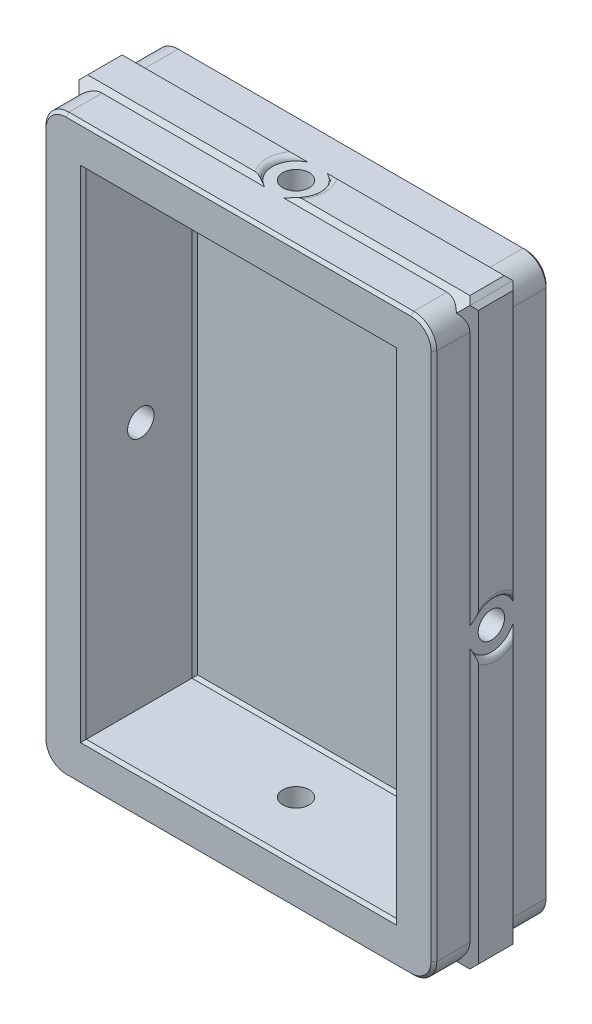
SolidWorks part; units mm, degrees
ref_plane "Front" through (0, 0, 0) normal (0, 0, 1) x (1, 0, 0)
ref_plane "Top" through (0, 0, 0) normal (0, 1, 0) x (1, 0, 0)
ref_plane "Right" through (0, 0, 0) normal (1, 0, 0) x (0, 0, -1)
sketch "Skizze1" plane through (0, 0, 0) normal (0, 0, 1) x (1, 0, 0)
  line L0 (61, 7) -> (7, 93) construction
  line L1 (0, 0) -> (68, 0)
  line L2 (0, 0) -> (0, 100)
  line L3 (0, 100) -> (68, 100)
  line L4 (68, 0) -> (68, 100)
  line L5 (11.1328, 7) -> (56.8672, 7)
  line L6 (7, 13.5818) -> (7, 86.4182)
  line L7 (11.1328, 93) -> (56.8672, 93)
  line L8 (61, 13.5818) -> (61, 86.4182)
  line L9 (61, 93) -> (7, 7) construction
  line L10 (11.1328, 93) -> (34, 56.5818)
  line L11 (7, 86.4182) -> (29.8672, 50)
  line L12 (56.8672, 93) -> (34, 56.5818)
  line L13 (11.1328, 7) -> (34, 43.4182)
  line L14 (38.1328, 50) -> (61, 86.4182)
  line L15 (38.1328, 50) -> (61, 13.5818)
  line L16 (29.8672, 50) -> (7, 13.5818)
  line L17 (34, 43.4182) -> (56.8672, 7)
  line L18 (7, 86.4182) -> (7, 93)
  line L19 (7, 93) -> (11.1328, 93)
  line L20 (56.8672, 93) -> (61, 93)
  line L21 (61, 93) -> (61, 86.4182)
  line L22 (61, 13.5818) -> (61, 7)
  line L23 (61, 7) -> (56.8672, 7)
  line L24 (11.1328, 7) -> (7, 7)
  line L25 (7, 7) -> (7, 13.5818)
  dimension "D1" = 7
  dimension "D2" = 7
  dimension "D3" = 7
  dimension "D4" = 7
  dimension "D5" = 3.5
  dimension "D6" = 3.5
  dimension "D7" = 3.5
  dimension "D8" = 3.5
extrude "Aufsatz-Linear austragen1" add sketch "Skizze1" along normal blind 20 contours L1 L4 L3 L2 L24 L25 L6 L18 L19 L7 L20 L21 L8 L22 L23 L5 region at (1.2093, 50, 0)
sketch "Skizze2" plane through (0, 0, 0) normal (0, 0, 1) x (1, 0, 0)
  line L1 (0, 100) -> (68, 100)
  line L2 (0, 100) -> (0, 0)
  line L3 (0, 0) -> (68, 0)
  line L4 (68, 100) -> (68, 0)
extrude "Aufsatz-Linear austragen2" add sketch "Skizze2" along normal blind 0.6
sketch "Skizze3" plane through (0, 0, 0) normal (0, -1, 0) x (1, 0, 0)
  line L0 (0, 10) -> (-11.2685, 10) construction
  line L1 (0, 20) -> (0, 0) construction
  line L2 (34, 0) -> (34, 20) construction
  line L5 (0, 13.75) -> (-0.75, 13)
  line L6 (-0.75, 13) -> (-0.75, 7)
  line L7 (0, 13.75) -> (0, 6.25)
  line L8 (0, 6.25) -> (-0.75, 7)
  line L9 (68, 13.75) -> (68.75, 13)
  line L10 (68.75, 13) -> (68.75, 7)
  line L11 (68, 6.25) -> (68.75, 7)
  line L12 (68, 13.75) -> (68, 6.25)
  line L13 (0, 20) -> (68, 20) construction
  line L14 (0, 0) -> (68, 0) construction
  point P15 (-0.75, 10)
  dimension "D1" = 45
  dimension "D2" = 7.5
  dimension "D3" = 0.75
extrude "Aufsatz-Linear austragen3" add sketch "Skizze3" against normal up to surface (100 mm away) up to face at (34, 100, 10)
sketch "Skizze4" plane through (0, 0, 0) normal (-1, 0, 0) x (0, 0, 1)
  line L0 (10, 100) -> (10, 106.8008) construction
  line L1 (7, 100) -> (13, 100) construction
  line L2 (13.75, 100) -> (13, 100.75)
  line L3 (13, 100.75) -> (7, 100.75)
  line L4 (13.75, 100) -> (6.25, 100)
  line L5 (6.25, 100) -> (7, 100.75)
  line L6 (0, 50) -> (20, 50) construction
  line L8 (13.75, 0) -> (13, -0.75)
  line L9 (13, -0.75) -> (7, -0.75)
  line L10 (6.25, 0) -> (7, -0.75)
  line L11 (13.75, 0) -> (6.25, 0)
  line L12 (0, 0) -> (0, 100) construction
  point P10 (10, 100.75)
  dimension "D1" = 0.75
  dimension "D2" = 45
extrude "Aufsatz-Linear austragen4" add sketch "Skizze4" against normal up to surface (68 mm away) up to face at (68, 50, 3.125)
sketch "Skizze5" plane through (0, 93, 0) normal (0, -1, 0) x (1, 0, 0)
  line L0 (34, 0) -> (34, 20) construction
  line L3 (0, 20) -> (68, 20) construction
  line L4 (0, 0) -> (68, 0) construction
  circle A0 centre (34, 10) radius 2.3
  dimension "D1" = 4.6
extrude "Schnitt-Linear austragen1" cut sketch "Skizze5" against normal blind 20
ref_plane "Ebene1" through (0, 50, 0) normal (0, 1, 0) x (1, 0, 0)
ref_plane "Ebene2" through (34, 0, 0) normal (-1, 0, 0) x (0, 0, 1)
sketch "Skizze6" plane through (7, 0, 0) normal (1, 0, 0) x (0, 0, -1)
  line L0 (-20, 50) -> (0, 50) construction
  line L3 (-20, 0) -> (-20, 100) construction
  line L4 (0, 0) -> (0, 100) construction
  circle A0 centre (-10, 50) radius 2.3
  dimension "D1" = 4.6
extrude "Schnitt-Linear austragen2" cut sketch "Skizze6" against normal blind 20
sketch "Skizze7" plane through (0, 100, 0) normal (0, 1, 0) x (1, 0, 0)
  circle A0 centre (34, -10) radius 4.1
  dimension "D1" = 8.2
extrude "Schnitt-Linear austragen3" cut sketch "Skizze7" along normal blind 20
sketch "Skizze8" plane through (0, 0, 0) normal (-1, 0, 0) x (0, 0, 1)
  line L1 (10, 52.3) -> (10, 47.7) construction
  circle A0 centre (10, 50) radius 4.1
  circle A1 centre (10, 50) radius 2.3 construction
  dimension "D1" = 8.2
extrude "Schnitt-Linear austragen4" cut sketch "Skizze8" along normal blind 20
mirror "Spiegeln1" about plane through (0, 50, 0) normal (0, 1, 0) of "Schnitt-Linear austragen3", "Schnitt-Linear austragen1"
mirror "Spiegeln2" about plane through (34, 0, 0) normal (-1, 0, 0) of "Schnitt-Linear austragen4", "Schnitt-Linear austragen2"
fillet "Verrundung1" radius 1 8 edges at (-0.75, 54.1, 10) (-0.75, 45.9, 10) (38.1, 100.75, 10) (29.9, 100.75, 10) (68.75, 54.1, 10) (68.75, 45.9, 10) (38.1, -0.75, 10) (29.9, -0.75, 10)
chamfer "Fase1" distance 0.75 angle 45 8 edges at (68.75, 100, 10) (68, 100.75, 10) (-0.75, 100, 10) (0, 100.75, 10) (0, -0.75, 10) (-0.75, 0, 10) (68.75, 0, 10) (68, -0.75, 10)
fillet "Verrundung2" radius 4 8 edges at (68, 0, 3.125) (68, 0, 16.875) (68, 100, 16.875) (68, 100, 3.125) (0, 100, 3.125) (0, 100, 16.875) (0, 0, 3.125) (0, 0, 16.875)
chamfer "Fase2" distance 0.5 angle 45 24 edges at (34, 7, 0.6) (7, 50, 0.6) (34, 93, 0.6) (61, 50, 0.6) (0, 50, 0) (1.1716, 1.1716, 0) (1.1716, 98.8284, 0) (34, 0, 0) (34, 100, 0) (66.8284, 1.1716, 0) (66.8284, 98.8284, 0) (68, 50, 0) (7, 50, 20) (68, 50, 20) (66.8284, 1.1716, 20) (66.8284, 98.8284, 20) (34, 0, 20) (34, 100, 20) (1.1716, 1.1716, 20) (1.1716, 98.8284, 20) (0, 50, 20) (34, 7, 20) (61, 50, 20) (34, 93, 20)
